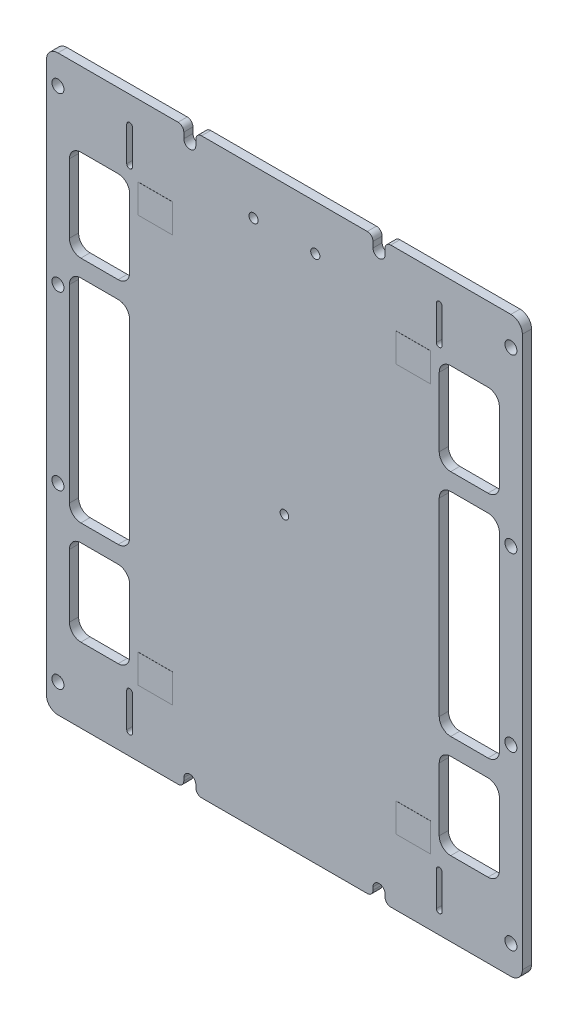
SolidWorks part; units mm, degrees
material "FR4_stuffedProtoboard"
ref_plane "Front Plane" through (0, 0, 0) normal (0, 0, 1) x (1, 0, 0)
ref_plane "Top Plane" through (0, 0, 0) normal (0, 1, 0) x (1, 0, 0)
ref_plane "Right Plane" through (0, 0, 0) normal (1, 0, 0) x (0, 0, -1)
sketch "Sketch1" plane through (0, 0, 0) normal (0, 0, 1) x (1, 0, 0)
  line L1 (-39.5, -50) -> (39.5, -50)
  line L2 (-41.5, -48) -> (-41.5, 48)
  line L3 (-39.5, 50) -> (39.5, 50)
  line L4 (41.5, -48) -> (41.5, 48)
  line L5 (-41.5, -50) -> (41.5, 50) construction
  line L6 (-41.5, 50) -> (41.5, -50) construction
  arc A0 (-39.5, -50) -> (-41.5, -48) centre (-39.5, -48) cw
  arc A1 (39.5, -50) -> (41.5, -48) centre (39.5, -48) ccw
  arc A2 (39.5, 50) -> (41.5, 48) centre (39.5, 48) cw
  arc A3 (-41.5, 48) -> (-39.5, 50) centre (-39.5, 48) cw
  point P0 (0, 0)
  dimension "D3" = 2
  dimension "D1" = 100
  dimension "D2" = 83
extrude "boardOutline" add sketch "Sketch1" along normal blind 1.6
sketch "Sketch2" plane through (0, 0, 1.6) normal (0, 0, 1) x (1, 0, 0)
  line L0 (39.5, 50) -> (-39.5, 50) construction
  line L1 (-41.5, 48) -> (-41.5, -48) construction
  line L2 (-5.385, 42.1) -> (5.385, 42.1) construction
  line L3 (-38, 44.2) -> (-38, 4.2) construction
  line L4 (0, 42.1) -> (0, 50) construction
  circle A0 centre (0, 0) radius 0.75
  circle A1 centre (-38, 44.2) radius 1.05 construction
  circle A2 centre (37.5, 44.2) radius 1.05 construction
  circle A3 centre (37.5, 4.2) radius 1.05 construction
  circle A4 centre (37.5, -35.8) radius 1.05 construction
  circle A5 centre (-38, 4.2) radius 1.05 construction
  circle A6 centre (-38, -35.8) radius 1.05 construction
  circle A7 centre (-5.385, 42.1) radius 0.8
  circle A8 centre (5.385, 42.1) radius 0.8
  dimension "D1" = 1.5
  dimension "D2" = 2.1
  dimension "D9" = 10.77
  dimension "D7" = 1.6
  dimension "D11" = 7.9
  dimension "D3" = 5.8
  dimension "D4" = 3.5
  dimension "D8" = 40
  dimension "D10" = 37.5
  dimension "D5" = 2
  dimension "D6" = 3
extrude "componentHoles" cut sketch "Sketch2" against normal through all
sketch "Sketch4" plane through (0, 0, 1.6) normal (0, 0, 1) x (1, 0, 0)
  line L0 (-27, 39.25) -> (-27, 45.25) construction
  line L1 (-27.5, 39.25) -> (-27.5, 45.25)
  line L2 (-26.5, 39.25) -> (-26.5, 45.25)
  line L3 (39.5, 50) -> (-39.5, 50) construction
  line L4 (-41.5, 48) -> (-41.5, -48) construction
  line L5 (27, 39.25) -> (27, 45.25) construction
  line L6 (26.5, 39.25) -> (26.5, 45.25)
  line L7 (27.5, 39.25) -> (27.5, 45.25)
  line L8 (27, -46.25) -> (27, -40.25) construction
  line L9 (26.5, -46.25) -> (26.5, -40.25)
  line L10 (27.5, -46.25) -> (27.5, -40.25)
  line L11 (-27, -46.25) -> (-27, -40.25) construction
  line L12 (-27.5, -46.25) -> (-27.5, -40.25)
  line L13 (-26.5, -46.25) -> (-26.5, -40.25)
  line L14 (-27, 39.25) -> (27, 39.25) construction
  line L15 (0, 39.25) -> (0, 50) construction
  arc A0 (-27.5, 39.25) -> (-26.5, 39.25) centre (-27, 39.25) ccw
  arc A1 (-26.5, 45.25) -> (-27.5, 45.25) centre (-27, 45.25) ccw
  arc A2 (26.5, 39.25) -> (27.5, 39.25) centre (27, 39.25) ccw
  arc A3 (27.5, 45.25) -> (26.5, 45.25) centre (27, 45.25) ccw
  arc A4 (26.5, -46.25) -> (27.5, -46.25) centre (27, -46.25) ccw
  arc A5 (27.5, -40.25) -> (26.5, -40.25) centre (27, -40.25) ccw
  arc A6 (-27.5, -46.25) -> (-26.5, -46.25) centre (-27, -46.25) ccw
  arc A7 (-26.5, -40.25) -> (-27.5, -40.25) centre (-27, -40.25) ccw
  point P2 (-27, 42.25)
  point P16 (27, 42.25)
  point P23 (27, -43.25)
  point P30 (-27, -43.25)
  dimension "D1" = 4.75
  dimension "D2" = 14
  dimension "D3" = 1
  dimension "D4" = 6
  dimension "D7" = 54
  dimension "D9" = 79.5
  dimension "D5" = 2
  dimension "D6" = 2
extrude "solarCellContactHoles" cut sketch "Sketch4" against normal blind 1.6
sketch "FrameLattice" plane through (0, 0, 0) normal (0, 0, 1) x (1, 0, 0)
  line L4 (-12.5, -19) -> (12.5, -19)
  line L5 (14.5, -17) -> (14.5, 16)
  line L6 (12.5, 18) -> (-12.5, 18)
  line L7 (-14.5, 16) -> (-14.5, -17)
  line L8 (-12.5, -19) -> (12.5, -19)
  line L9 (14.5, -17) -> (14.5, 16)
  line L10 (12.5, 18) -> (-12.5, 18)
  line L11 (-14.5, 16) -> (-14.5, -17)
  line L12 (-12.5, -92) -> (12.5, -92)
  line L13 (14.5, -90) -> (14.5, -69)
  line L14 (12.5, -67) -> (-12.5, -67)
  line L15 (-14.5, -69) -> (-14.5, -90)
  line L16 (-12.5, -92) -> (12.5, -92)
  line L17 (14.5, -90) -> (14.5, -69)
  line L18 (12.5, -67) -> (-12.5, -67)
  line L19 (-14.5, -69) -> (-14.5, -90)
  line L20 (-35.5, -132) -> (-19.5, -132)
  line L21 (-17.5, -130) -> (-17.5, -97)
  line L22 (-19.5, -95) -> (-35.5, -95)
  line L23 (-37.5, -97) -> (-37.5, -130)
  line L24 (-35.5, -132) -> (-19.5, -132)
  line L25 (-17.5, -130) -> (-17.5, -97)
  line L26 (-19.5, -95) -> (-35.5, -95)
  line L27 (-37.5, -97) -> (-37.5, -130)
  line L28 (19.5, -160) -> (35.5, -160)
  line L29 (37.5, -158) -> (37.5, -137)
  line L30 (35.5, -135) -> (19.5, -135)
  line L31 (17.5, -137) -> (17.5, -158)
  line L32 (19.5, -160) -> (35.5, -160)
  line L33 (37.5, -158) -> (37.5, -137)
  line L34 (35.5, -135) -> (19.5, -135)
  line L35 (17.5, -137) -> (17.5, -158)
  line L36 (19.5, -92) -> (35.5, -92)
  line L37 (37.5, -90) -> (37.5, -69)
  line L38 (35.5, -67) -> (19.5, -67)
  line L39 (17.5, -69) -> (17.5, -90)
  line L40 (19.5, -92) -> (35.5, -92)
  line L41 (37.5, -90) -> (37.5, -69)
  line L42 (35.5, -67) -> (19.5, -67)
  line L43 (17.5, -69) -> (17.5, -90)
  line L44 (-35.5, -92) -> (-19.5, -92)
  line L45 (-17.5, -90) -> (-17.5, -69)
  line L46 (-19.5, -67) -> (-35.5, -67)
  line L47 (-37.5, -69) -> (-37.5, -90)
  line L48 (-35.5, -92) -> (-19.5, -92)
  line L49 (-17.5, -90) -> (-17.5, -69)
  line L50 (-19.5, -67) -> (-35.5, -67)
  line L51 (-37.5, -69) -> (-37.5, -90)
  line L52 (19.5, -132) -> (35.5, -132)
  line L53 (37.5, -130) -> (37.5, -97)
  line L54 (35.5, -95) -> (19.5, -95)
  line L55 (17.5, -97) -> (17.5, -130)
  line L56 (19.5, -132) -> (35.5, -132)
  line L57 (37.5, -130) -> (37.5, -97)
  line L58 (35.5, -95) -> (19.5, -95)
  line L59 (17.5, -97) -> (17.5, -130)
  line L60 (-12.5, -160) -> (12.5, -160)
  line L61 (14.5, -158) -> (14.5, -137)
  line L62 (12.5, -135) -> (-12.5, -135)
  line L63 (-14.5, -137) -> (-14.5, -158)
  line L65 (14.5, -158) -> (14.5, -137)
  line L66 (12.5, -135) -> (-12.5, -135)
  line L67 (-14.5, -137) -> (-14.5, -158)
  line L68 (-26.75, -62) -> (-26.75, -52)
  line L69 (-28.75, -50) -> (-35, -50)
  line L70 (-37, -52) -> (-37, -62)
  line L71 (-35, -64) -> (-28.75, -64)
  line L72 (-26.75, -62) -> (-26.75, -52)
  line L73 (-28.75, -50) -> (-35, -50)
  line L74 (-37, -52) -> (-37, -62)
  line L75 (-35, -64) -> (-28.75, -64)
  line L76 (-35.5, -160) -> (-19.5, -160)
  line L77 (-17.5, -158) -> (-17.5, -137)
  line L78 (-19.5, -135) -> (-35.5, -135)
  line L79 (-37.5, -137) -> (-37.5, -158)
  line L80 (-35.5, -160) -> (-19.5, -160)
  line L81 (-17.5, -158) -> (-17.5, -137)
  line L82 (-19.5, -135) -> (-35.5, -135)
  line L83 (-37.5, -137) -> (-37.5, -158)
  line L84 (-12.5, -132) -> (12.5, -132)
  line L85 (14.5, -130) -> (14.5, -97)
  line L86 (12.5, -95) -> (-12.5, -95)
  line L87 (-14.5, -97) -> (-14.5, -130)
  line L88 (-12.5, -132) -> (12.5, -132)
  line L89 (14.5, -130) -> (14.5, -97)
  line L90 (12.5, -95) -> (-12.5, -95)
  line L91 (-14.5, -97) -> (-14.5, -130)
  line L92 (-35.5, -19) -> (-19.5, -19)
  line L93 (-17.5, -17) -> (-17.5, 16)
  line L94 (-19.5, 18) -> (-35.5, 18)
  line L95 (-37.5, 16) -> (-37.5, -17)
  line L96 (-35.5, -19) -> (-19.5, -19)
  line L97 (-17.5, -17) -> (-17.5, 16)
  line L98 (-19.5, 18) -> (-35.5, 18)
  line L99 (-37.5, 16) -> (-37.5, -17)
  line L100 (19.5, -47) -> (35.5, -47)
  line L101 (37.5, -45) -> (37.5, -24)
  line L102 (35.5, -22) -> (19.5, -22)
  line L103 (17.5, -24) -> (17.5, -45)
  line L104 (19.5, -47) -> (35.5, -47)
  line L105 (37.5, -45) -> (37.5, -24)
  line L106 (35.5, -22) -> (19.5, -22)
  line L107 (17.5, -24) -> (17.5, -45)
  line L108 (-12.5, -47) -> (12.5, -47)
  line L109 (14.5, -45) -> (14.5, -24)
  line L110 (12.5, -22) -> (-12.5, -22)
  line L111 (-14.5, -24) -> (-14.5, -45)
  line L112 (-12.5, -47) -> (12.5, -47)
  line L113 (14.5, -45) -> (14.5, -24)
  line L114 (12.5, -22) -> (-12.5, -22)
  line L115 (-14.5, -24) -> (-14.5, -45)
  line L116 (-35.5, -47) -> (-19.5, -47)
  line L117 (-17.5, -45) -> (-17.5, -24)
  line L118 (-19.5, -22) -> (-35.5, -22)
  line L119 (-37.5, -24) -> (-37.5, -45)
  line L120 (-35.5, -47) -> (-19.5, -47)
  line L121 (-17.5, -45) -> (-17.5, -24)
  line L122 (-19.5, -22) -> (-35.5, -22)
  line L123 (-37.5, -24) -> (-37.5, -45)
  line L124 (19.5, -19) -> (35.5, -19)
  line L125 (37.5, -17) -> (37.5, 16)
  line L126 (35.5, 18) -> (19.5, 18)
  line L127 (17.5, 16) -> (17.5, -17)
  line L128 (19.5, -19) -> (35.5, -19)
  line L129 (37.5, -17) -> (37.5, 16)
  line L130 (35.5, 18) -> (19.5, 18)
  line L131 (17.5, 16) -> (17.5, -17)
  line L132 (-35.5, 21) -> (-19.5, 21)
  line L133 (-17.5, 23) -> (-17.5, 44)
  line L134 (-19.5, 46) -> (-35.5, 46)
  line L135 (-37.5, 44) -> (-37.5, 23)
  line L136 (-35.5, 21) -> (-19.5, 21)
  line L137 (-17.5, 23) -> (-17.5, 44)
  line L138 (-19.5, 46) -> (-35.5, 46)
  line L139 (-37.5, 44) -> (-37.5, 23)
  line L140 (-12.5, 21) -> (12.5, 21)
  line L141 (14.5, 23) -> (14.5, 44)
  line L142 (12.5, 46) -> (-12.5, 46)
  line L143 (-14.5, 44) -> (-14.5, 23)
  line L144 (-12.5, 21) -> (12.5, 21)
  line L145 (14.5, 23) -> (14.5, 44)
  line L147 (-14.5, 44) -> (-14.5, 23)
  line L148 (19.5, 21) -> (35.5, 21)
  line L149 (37.5, 23) -> (37.5, 44)
  line L150 (35.5, 46) -> (19.5, 46)
  line L151 (17.5, 44) -> (17.5, 23)
  line L152 (19.5, 21) -> (35.5, 21)
  line L153 (37.5, 23) -> (37.5, 44)
  line L154 (35.5, 46) -> (19.5, 46)
  line L155 (17.5, 44) -> (17.5, 23)
  line L156 (-3.5, -62) -> (-3.5, -52)
  line L157 (-5.5, -50) -> (-13, -50)
  line L158 (-15, -52) -> (-15, -62)
  line L159 (-13, -64) -> (-5.5, -64)
  line L160 (-3.5, -62) -> (-3.5, -52)
  line L161 (-5.5, -50) -> (-13, -50)
  line L162 (-15, -52) -> (-15, -62)
  line L163 (-13, -64) -> (-5.5, -64)
  line L164 (28.75, -64) -> (35, -64)
  line L165 (37, -62) -> (37, -52)
  line L166 (35, -50) -> (28.75, -50)
  line L167 (26.75, -52) -> (26.75, -62)
  line L168 (28.75, -64) -> (35, -64)
  line L169 (37, -62) -> (37, -52)
  line L170 (35, -50) -> (28.75, -50)
  line L171 (26.75, -52) -> (26.75, -62)
  line L172 (5.5, -64) -> (13, -64)
  line L173 (15, -62) -> (15, -52)
  line L174 (13, -50) -> (5.5, -50)
  line L175 (3.5, -52) -> (3.5, -62)
  line L176 (5.5, -64) -> (13, -64)
  line L177 (15, -62) -> (15, -52)
  line L178 (13, -50) -> (5.5, -50)
  line L179 (3.5, -52) -> (3.5, -62)
  line L212 (-12.5, -160) -> (12.5, -160)
  line L213 (12.5, 46) -> (-12.5, 46)
  circle A2 centre (-16.5, 48) radius 0.8
  circle A3 centre (-16.5, 48) radius 0.8
  circle A4 centre (-16.5, -162) radius 0.8
  arc A5 (12.5, -19) -> (14.5, -17) centre (12.5, -17) ccw
  arc A6 (14.5, 16) -> (12.5, 18) centre (12.5, 16) ccw
  arc A7 (-12.5, 18) -> (-14.5, 16) centre (-12.5, 16) ccw
  arc A8 (-14.5, -17) -> (-12.5, -19) centre (-12.5, -17) ccw
  arc A9 (12.5, -19) -> (14.5, -17) centre (12.5, -17) ccw
  arc A10 (14.5, 16) -> (12.5, 18) centre (12.5, 16) ccw
  arc A11 (-12.5, 18) -> (-14.5, 16) centre (-12.5, 16) ccw
  arc A12 (-14.5, -17) -> (-12.5, -19) centre (-12.5, -17) ccw
  arc A13 (12.5, -92) -> (14.5, -90) centre (12.5, -90) ccw
  arc A14 (14.5, -69) -> (12.5, -67) centre (12.5, -69) ccw
  arc A15 (-12.5, -67) -> (-14.5, -69) centre (-12.5, -69) ccw
  arc A16 (-14.5, -90) -> (-12.5, -92) centre (-12.5, -90) ccw
  arc A17 (12.5, -92) -> (14.5, -90) centre (12.5, -90) ccw
  arc A18 (14.5, -69) -> (12.5, -67) centre (12.5, -69) ccw
  arc A19 (-12.5, -67) -> (-14.5, -69) centre (-12.5, -69) ccw
  arc A20 (-14.5, -90) -> (-12.5, -92) centre (-12.5, -90) ccw
  arc A21 (-19.5, -132) -> (-17.5, -130) centre (-19.5, -130) ccw
  arc A22 (-17.5, -97) -> (-19.5, -95) centre (-19.5, -97) ccw
  arc A23 (-35.5, -95) -> (-37.5, -97) centre (-35.5, -97) ccw
  arc A24 (-37.5, -130) -> (-35.5, -132) centre (-35.5, -130) ccw
  arc A25 (-19.5, -132) -> (-17.5, -130) centre (-19.5, -130) ccw
  arc A26 (-17.5, -97) -> (-19.5, -95) centre (-19.5, -97) ccw
  arc A27 (-35.5, -95) -> (-37.5, -97) centre (-35.5, -97) ccw
  arc A28 (-37.5, -130) -> (-35.5, -132) centre (-35.5, -130) ccw
  arc A29 (35.5, -160) -> (37.5, -158) centre (35.5, -158) ccw
  arc A30 (37.5, -137) -> (35.5, -135) centre (35.5, -137) ccw
  arc A31 (19.5, -135) -> (17.5, -137) centre (19.5, -137) ccw
  arc A32 (17.5, -158) -> (19.5, -160) centre (19.5, -158) ccw
  arc A33 (35.5, -160) -> (37.5, -158) centre (35.5, -158) ccw
  arc A34 (37.5, -137) -> (35.5, -135) centre (35.5, -137) ccw
  arc A35 (19.5, -135) -> (17.5, -137) centre (19.5, -137) ccw
  arc A36 (17.5, -158) -> (19.5, -160) centre (19.5, -158) ccw
  arc A37 (35.5, -92) -> (37.5, -90) centre (35.5, -90) ccw
  arc A38 (37.5, -69) -> (35.5, -67) centre (35.5, -69) ccw
  arc A39 (19.5, -67) -> (17.5, -69) centre (19.5, -69) ccw
  arc A40 (17.5, -90) -> (19.5, -92) centre (19.5, -90) ccw
  arc A41 (35.5, -92) -> (37.5, -90) centre (35.5, -90) ccw
  arc A42 (37.5, -69) -> (35.5, -67) centre (35.5, -69) ccw
  arc A43 (19.5, -67) -> (17.5, -69) centre (19.5, -69) ccw
  arc A44 (17.5, -90) -> (19.5, -92) centre (19.5, -90) ccw
  arc A45 (-19.5, -92) -> (-17.5, -90) centre (-19.5, -90) ccw
  arc A46 (-17.5, -69) -> (-19.5, -67) centre (-19.5, -69) ccw
  arc A47 (-35.5, -67) -> (-37.5, -69) centre (-35.5, -69) ccw
  arc A48 (-37.5, -90) -> (-35.5, -92) centre (-35.5, -90) ccw
  arc A49 (-19.5, -92) -> (-17.5, -90) centre (-19.5, -90) ccw
  arc A50 (-17.5, -69) -> (-19.5, -67) centre (-19.5, -69) ccw
  arc A51 (-35.5, -67) -> (-37.5, -69) centre (-35.5, -69) ccw
  arc A52 (-37.5, -90) -> (-35.5, -92) centre (-35.5, -90) ccw
  arc A53 (35.5, -132) -> (37.5, -130) centre (35.5, -130) ccw
  arc A54 (37.5, -97) -> (35.5, -95) centre (35.5, -97) ccw
  arc A55 (19.5, -95) -> (17.5, -97) centre (19.5, -97) ccw
  arc A56 (17.5, -130) -> (19.5, -132) centre (19.5, -130) ccw
  arc A57 (35.5, -132) -> (37.5, -130) centre (35.5, -130) ccw
  arc A58 (37.5, -97) -> (35.5, -95) centre (35.5, -97) ccw
  arc A59 (19.5, -95) -> (17.5, -97) centre (19.5, -97) ccw
  arc A60 (17.5, -130) -> (19.5, -132) centre (19.5, -130) ccw
  arc A61 (12.5, -160) -> (14.5, -158) centre (12.5, -158) ccw
  arc A62 (14.5, -137) -> (12.5, -135) centre (12.5, -137) ccw
  arc A63 (-12.5, -135) -> (-14.5, -137) centre (-12.5, -137) ccw
  arc A64 (-14.5, -158) -> (-12.5, -160) centre (-12.5, -158) ccw
  arc A65 (12.5, -160) -> (14.5, -158) centre (12.5, -158) ccw
  arc A66 (14.5, -137) -> (12.5, -135) centre (12.5, -137) ccw
  arc A67 (-12.5, -135) -> (-14.5, -137) centre (-12.5, -137) ccw
  arc A68 (-14.5, -158) -> (-12.5, -160) centre (-12.5, -158) ccw
  circle A69 centre (-16.5, -162) radius 0.8
  circle A70 centre (16.5, -162) radius 0.8
  circle A71 centre (16.5, -162) radius 0.8
  circle A72 centre (-16.5, -65.5) radius 0.8
  circle A73 centre (-16.5, -65.5) radius 0.8
  circle A74 centre (16.5, -65.5) radius 0.8
  circle A75 centre (16.5, -65.5) radius 0.8
  circle A76 centre (-39.5, -129) radius 0.8
  circle A77 centre (-39.5, -129) radius 0.8
  circle A78 centre (39.5, -159) radius 0.8
  circle A79 centre (39.5, -159) radius 0.8
  circle A80 centre (-39.5, -159) radius 0.8
  circle A81 centre (-39.5, -159) radius 0.8
  circle A82 centre (39.5, -129) radius 0.8
  circle A83 centre (39.5, -129) radius 0.8
  circle A84 centre (39.5, -99) radius 0.8
  circle A85 centre (39.5, -99) radius 0.8
  circle A86 centre (-39.5, -99) radius 0.8
  circle A87 centre (-39.5, -99) radius 0.8
  circle A88 centre (-39.5, -69) radius 0.8
  circle A89 centre (-39.5, -69) radius 0.8
  circle A90 centre (39.5, -69) radius 0.8
  circle A91 centre (39.5, -69) radius 0.8
  circle A92 centre (39.5, -15) radius 0.8
  circle A93 centre (39.5, -15) radius 0.8
  circle A94 centre (39.5, 15) radius 0.8
  arc A95 (-26.75, -52) -> (-28.75, -50) centre (-28.75, -52) ccw
  arc A96 (-35, -50) -> (-37, -52) centre (-35, -52) ccw
  arc A97 (-37, -62) -> (-35, -64) centre (-35, -62) ccw
  arc A98 (-28.75, -64) -> (-26.75, -62) centre (-28.75, -62) ccw
  arc A99 (-26.75, -52) -> (-28.75, -50) centre (-28.75, -52) ccw
  arc A100 (-35, -50) -> (-37, -52) centre (-35, -52) ccw
  arc A101 (-37, -62) -> (-35, -64) centre (-35, -62) ccw
  arc A102 (-28.75, -64) -> (-26.75, -62) centre (-28.75, -62) ccw
  arc A103 (-19.5, -160) -> (-17.5, -158) centre (-19.5, -158) ccw
  arc A104 (-17.5, -137) -> (-19.5, -135) centre (-19.5, -137) ccw
  arc A105 (-35.5, -135) -> (-37.5, -137) centre (-35.5, -137) ccw
  arc A106 (-37.5, -158) -> (-35.5, -160) centre (-35.5, -158) ccw
  arc A107 (-19.5, -160) -> (-17.5, -158) centre (-19.5, -158) ccw
  arc A108 (-17.5, -137) -> (-19.5, -135) centre (-19.5, -137) ccw
  arc A109 (-35.5, -135) -> (-37.5, -137) centre (-35.5, -137) ccw
  arc A110 (-37.5, -158) -> (-35.5, -160) centre (-35.5, -158) ccw
  arc A111 (12.5, -132) -> (14.5, -130) centre (12.5, -130) ccw
  arc A112 (14.5, -97) -> (12.5, -95) centre (12.5, -97) ccw
  arc A113 (-12.5, -95) -> (-14.5, -97) centre (-12.5, -97) ccw
  arc A114 (-14.5, -130) -> (-12.5, -132) centre (-12.5, -130) ccw
  arc A115 (12.5, -132) -> (14.5, -130) centre (12.5, -130) ccw
  arc A116 (14.5, -97) -> (12.5, -95) centre (12.5, -97) ccw
  arc A117 (-12.5, -95) -> (-14.5, -97) centre (-12.5, -97) ccw
  arc A118 (-14.5, -130) -> (-12.5, -132) centre (-12.5, -130) ccw
  arc A119 (-19.5, -19) -> (-17.5, -17) centre (-19.5, -17) ccw
  arc A120 (-17.5, 16) -> (-19.5, 18) centre (-19.5, 16) ccw
  arc A121 (-35.5, 18) -> (-37.5, 16) centre (-35.5, 16) ccw
  arc A122 (-37.5, -17) -> (-35.5, -19) centre (-35.5, -17) ccw
  arc A123 (-19.5, -19) -> (-17.5, -17) centre (-19.5, -17) ccw
  arc A124 (-17.5, 16) -> (-19.5, 18) centre (-19.5, 16) ccw
  arc A125 (-35.5, 18) -> (-37.5, 16) centre (-35.5, 16) ccw
  arc A126 (-37.5, -17) -> (-35.5, -19) centre (-35.5, -17) ccw
  arc A127 (35.5, -47) -> (37.5, -45) centre (35.5, -45) ccw
  arc A128 (37.5, -24) -> (35.5, -22) centre (35.5, -24) ccw
  arc A129 (19.5, -22) -> (17.5, -24) centre (19.5, -24) ccw
  arc A130 (17.5, -45) -> (19.5, -47) centre (19.5, -45) ccw
  arc A131 (35.5, -47) -> (37.5, -45) centre (35.5, -45) ccw
  arc A132 (37.5, -24) -> (35.5, -22) centre (35.5, -24) ccw
  arc A133 (19.5, -22) -> (17.5, -24) centre (19.5, -24) ccw
  arc A134 (17.5, -45) -> (19.5, -47) centre (19.5, -45) ccw
  arc A135 (12.5, -47) -> (14.5, -45) centre (12.5, -45) ccw
  arc A136 (14.5, -24) -> (12.5, -22) centre (12.5, -24) ccw
  arc A137 (-12.5, -22) -> (-14.5, -24) centre (-12.5, -24) ccw
  arc A138 (-14.5, -45) -> (-12.5, -47) centre (-12.5, -45) ccw
  arc A139 (12.5, -47) -> (14.5, -45) centre (12.5, -45) ccw
  arc A140 (14.5, -24) -> (12.5, -22) centre (12.5, -24) ccw
  arc A141 (-12.5, -22) -> (-14.5, -24) centre (-12.5, -24) ccw
  arc A142 (-14.5, -45) -> (-12.5, -47) centre (-12.5, -45) ccw
  arc A143 (-19.5, -47) -> (-17.5, -45) centre (-19.5, -45) ccw
  arc A144 (-17.5, -24) -> (-19.5, -22) centre (-19.5, -24) ccw
  arc A145 (-35.5, -22) -> (-37.5, -24) centre (-35.5, -24) ccw
  arc A146 (-37.5, -45) -> (-35.5, -47) centre (-35.5, -45) ccw
  arc A147 (-19.5, -47) -> (-17.5, -45) centre (-19.5, -45) ccw
  arc A148 (-17.5, -24) -> (-19.5, -22) centre (-19.5, -24) ccw
  arc A149 (-35.5, -22) -> (-37.5, -24) centre (-35.5, -24) ccw
  arc A150 (-37.5, -45) -> (-35.5, -47) centre (-35.5, -45) ccw
  arc A151 (35.5, -19) -> (37.5, -17) centre (35.5, -17) ccw
  arc A152 (37.5, 16) -> (35.5, 18) centre (35.5, 16) ccw
  arc A153 (19.5, 18) -> (17.5, 16) centre (19.5, 16) ccw
  arc A154 (17.5, -17) -> (19.5, -19) centre (19.5, -17) ccw
  arc A155 (35.5, -19) -> (37.5, -17) centre (35.5, -17) ccw
  arc A156 (37.5, 16) -> (35.5, 18) centre (35.5, 16) ccw
  arc A157 (19.5, 18) -> (17.5, 16) centre (19.5, 16) ccw
  arc A158 (17.5, -17) -> (19.5, -19) centre (19.5, -17) ccw
  arc A159 (-19.5, 21) -> (-17.5, 23) centre (-19.5, 23) ccw
  arc A160 (-17.5, 44) -> (-19.5, 46) centre (-19.5, 44) ccw
  arc A161 (-35.5, 46) -> (-37.5, 44) centre (-35.5, 44) ccw
  arc A162 (-37.5, 23) -> (-35.5, 21) centre (-35.5, 23) ccw
  arc A163 (-19.5, 21) -> (-17.5, 23) centre (-19.5, 23) ccw
  arc A164 (-17.5, 44) -> (-19.5, 46) centre (-19.5, 44) ccw
  arc A165 (-35.5, 46) -> (-37.5, 44) centre (-35.5, 44) ccw
  arc A166 (-37.5, 23) -> (-35.5, 21) centre (-35.5, 23) ccw
  arc A167 (12.5, 21) -> (14.5, 23) centre (12.5, 23) ccw
  arc A168 (14.5, 44) -> (12.5, 46) centre (12.5, 44) ccw
  arc A169 (-12.5, 46) -> (-14.5, 44) centre (-12.5, 44) ccw
  arc A170 (-14.5, 23) -> (-12.5, 21) centre (-12.5, 23) ccw
  arc A171 (12.5, 21) -> (14.5, 23) centre (12.5, 23) ccw
  arc A172 (14.5, 44) -> (12.5, 46) centre (12.5, 44) ccw
  arc A173 (-12.5, 46) -> (-14.5, 44) centre (-12.5, 44) ccw
  arc A174 (-14.5, 23) -> (-12.5, 21) centre (-12.5, 23) ccw
  arc A175 (35.5, 21) -> (37.5, 23) centre (35.5, 23) ccw
  arc A176 (37.5, 44) -> (35.5, 46) centre (35.5, 44) ccw
  arc A177 (19.5, 46) -> (17.5, 44) centre (19.5, 44) ccw
  arc A178 (17.5, 23) -> (19.5, 21) centre (19.5, 23) ccw
  arc A179 (35.5, 21) -> (37.5, 23) centre (35.5, 23) ccw
  arc A180 (37.5, 44) -> (35.5, 46) centre (35.5, 44) ccw
  arc A181 (19.5, 46) -> (17.5, 44) centre (19.5, 44) ccw
  arc A182 (17.5, 23) -> (19.5, 21) centre (19.5, 23) ccw
  circle A183 centre (39.5, 15) radius 0.8
  circle A184 centre (-39.5, 45) radius 0.8
  circle A185 centre (-39.5, 45) radius 0.8
  circle A186 centre (39.5, 45) radius 0.8
  circle A187 centre (39.5, 45) radius 0.8
  circle A188 centre (-39.5, 15) radius 0.8
  circle A189 centre (-39.5, 15) radius 0.8
  circle A190 centre (16.5, -48.5) radius 0.8
  circle A191 centre (16.5, -48.5) radius 0.8
  circle A192 centre (-16.5, -48.5) radius 0.8
  circle A193 centre (-16.5, -48.5) radius 0.8
  circle A194 centre (16.5, 48) radius 0.8
  circle A195 centre (16.5, 48) radius 0.8
  circle A196 centre (-39.5, -15) radius 0.8
  circle A197 centre (-39.5, -15) radius 0.8
  circle A198 centre (-22, -61) radius 2.75
  circle A199 centre (-22, -61) radius 2.75
  circle A200 centre (-22, -53) radius 2.75
  circle A201 centre (-22, -53) radius 2.75
  circle A202 centre (22, -53) radius 2.75
  circle A203 centre (22, -53) radius 2.75
  circle A204 centre (22, -61) radius 2.75
  arc A205 (-3.5, -52) -> (-5.5, -50) centre (-5.5, -52) ccw
  arc A206 (-13, -50) -> (-15, -52) centre (-13, -52) ccw
  arc A207 (-15, -62) -> (-13, -64) centre (-13, -62) ccw
  arc A208 (-5.5, -64) -> (-3.5, -62) centre (-5.5, -62) ccw
  arc A209 (-3.5, -52) -> (-5.5, -50) centre (-5.5, -52) ccw
  arc A210 (-13, -50) -> (-15, -52) centre (-13, -52) ccw
  arc A211 (-15, -62) -> (-13, -64) centre (-13, -62) ccw
  arc A212 (-5.5, -64) -> (-3.5, -62) centre (-5.5, -62) ccw
  circle A213 centre (22, -61) radius 2.75
  circle A214 centre (0, -57) radius 2.75
  circle A215 centre (0, -57) radius 2.75
  circle A216 centre (39.5, -45) radius 0.8
  circle A217 centre (39.5, -45) radius 0.8
  circle A218 centre (-39.5, -45) radius 0.8
  arc A219 (35, -64) -> (37, -62) centre (35, -62) ccw
  arc A220 (37, -52) -> (35, -50) centre (35, -52) ccw
  arc A221 (28.75, -50) -> (26.75, -52) centre (28.75, -52) ccw
  arc A222 (26.75, -62) -> (28.75, -64) centre (28.75, -62) ccw
  arc A223 (35, -64) -> (37, -62) centre (35, -62) ccw
  arc A224 (37, -52) -> (35, -50) centre (35, -52) ccw
  arc A225 (28.75, -50) -> (26.75, -52) centre (28.75, -52) ccw
  arc A226 (26.75, -62) -> (28.75, -64) centre (28.75, -62) ccw
  arc A227 (13, -64) -> (15, -62) centre (13, -62) ccw
  arc A228 (15, -52) -> (13, -50) centre (13, -52) ccw
  arc A229 (5.5, -50) -> (3.5, -52) centre (5.5, -52) ccw
  arc A230 (3.5, -62) -> (5.5, -64) centre (5.5, -62) ccw
  arc A231 (13, -64) -> (15, -62) centre (13, -62) ccw
  arc A232 (15, -52) -> (13, -50) centre (13, -52) ccw
  arc A233 (5.5, -50) -> (3.5, -52) centre (5.5, -52) ccw
  arc A234 (3.5, -62) -> (5.5, -64) centre (5.5, -62) ccw
  circle A235 centre (-39.5, -45) radius 0.8
  dimension "D1" = 0
  dimension "D2" = 0
  dimension "D3" = 0
  dimension "D4" = 0
  dimension "D5" = 0
  dimension "D6" = 0
  dimension "D7" = 0
  dimension "D8" = 0
  dimension "D9" = 0
  dimension "D10" = 0
  dimension "D11" = 0
  dimension "D12" = 0
  dimension "D13" = 0
  dimension "D14" = 0
  dimension "D15" = 0
  dimension "D16" = 0
  dimension "D17" = 0
  dimension "D18" = 0
  dimension "D19" = 0
  dimension "D20" = 0
  dimension "D21" = 0
  dimension "D22" = 0
  dimension "D23" = 0
  dimension "D24" = 0
  dimension "D25" = 0
  dimension "D26" = 0
  dimension "D27" = 0
  dimension "D28" = 0
  dimension "D29" = 0
  dimension "D30" = 0
  dimension "D31" = 0
  dimension "D32" = 0
  dimension "D33" = 0
  dimension "D34" = 0
  dimension "D35" = 0
  dimension "D36" = 0
  dimension "D37" = 0
  dimension "D38" = 0
  dimension "D39" = 0
  dimension "D40" = 0
  dimension "D41" = 0
  dimension "D42" = 0
  dimension "D43" = 0
  dimension "D44" = 0
  dimension "D45" = 0
  dimension "D46" = 0
  dimension "D47" = 0
  dimension "D48" = 0
  dimension "D49" = 0
  dimension "D50" = 0
  dimension "D51" = 0
sketch "Sketch3" plane through (0, 0, 1.6) normal (0, 0, 1) x (1, 0, 0)
  line L0 (-35.5, -19) -> (-19.5, -19) construction
  line L1 (-35.5, 37) -> (-29, 37)
  line L2 (-37.5, 35) -> (-37.5, 23)
  line L3 (-35.5, 21) -> (-29, 21)
  line L4 (-27, 35) -> (-27, 23)
  line L6 (-29, -22) -> (-35.5, -22)
  line L7 (-37.5, 16) -> (-37.5, -17) construction
  line L8 (-19.5, -22) -> (-35.5, -22) construction
  line L9 (0, 50) -> (0, -50) construction
  line L10 (39.5, 50) -> (-39.5, 50) construction
  line L11 (-39.5, -50) -> (39.5, -50) construction
  line L12 (-27, -24) -> (-27, -35)
  line L13 (-29, -37) -> (-35.5, -37)
  line L14 (-37.5, -24) -> (-37.5, -35)
  line L15 (-19.5, 18) -> (-35.5, 18) construction
  line L16 (-35.5, 21) -> (-19.5, 21) construction
  line L19 (-29, -19) -> (-35.5, -19)
  line L25 (-27, -17) -> (-27, 16)
  line L26 (-29, 18) -> (-35.5, 18)
  line L27 (-37.5, -17) -> (-37.5, 16)
  arc A0 (-37.5, 23) -> (-35.5, 21) centre (-35.5, 23) ccw
  arc A1 (-29, 21) -> (-27, 23) centre (-29, 23) ccw
  arc A2 (-29, 37) -> (-27, 35) centre (-29, 35) cw
  arc A3 (-35.5, 37) -> (-37.5, 35) centre (-35.5, 35) ccw
  arc A4 (-29, -19) -> (-27, -17) centre (-29, -17) ccw
  arc A5 (-27, -35) -> (-29, -37) centre (-29, -35) cw
  arc A6 (-35.5, -37) -> (-37.5, -35) centre (-35.5, -35) cw
  arc A7 (-35.5, -22) -> (-37.5, -24) centre (-35.5, -24) ccw
  arc A8 (-29, -22) -> (-27, -24) centre (-29, -24) cw
  arc A9 (-37.5, 23) -> (-35.5, 21) centre (-35.5, 23) ccw construction
  arc A17 (-35.5, -19) -> (-37.5, -17) centre (-35.5, -17) cw
  arc A18 (-35.5, 18) -> (-37.5, 16) centre (-35.5, 16) ccw
  arc A19 (-27, 16) -> (-29, 18) centre (-29, 16) ccw
  point P12 (-27, 21)
  point P15 (-27, 37)
  point P18 (-37.5, 37)
  dimension "D10" = 13
  dimension "D1" = 10.5
  dimension "D3" = 13
extrude "windows_1side" cut sketch "Sketch3" against normal through all
sketch "Sketch5" plane through (0, 0, 1.6) normal (0, 0, 1) x (1, 0, 0)
  line L0 (-41.5, 48) -> (-41.5, -48) construction
  line L1 (-25.5, 37.5) -> (-19.5, 37.5)
  line L2 (-25.5, 37.5) -> (-25.5, 32.5)
  line L3 (-25.5, 32.5) -> (-19.5, 32.5)
  line L4 (-19.5, 37.5) -> (-19.5, 32.5)
  line L5 (0, 37.5) -> (0, 50) construction
  line L6 (19.5, 37.5) -> (19.5, 32.5)
  line L7 (25.5, 37.5) -> (25.5, 32.5)
  line L8 (19.5, 32.5) -> (25.5, 32.5)
  line L9 (19.5, 37.5) -> (25.5, 37.5)
  line L10 (19.5, -33.5) -> (19.5, -38.5)
  line L11 (25.5, -33.5) -> (25.5, -38.5)
  line L12 (19.5, -38.5) -> (25.5, -38.5)
  line L13 (19.5, -33.5) -> (25.5, -33.5)
  line L14 (-25.5, -33.5) -> (-25.5, -38.5)
  line L15 (-19.5, -33.5) -> (-19.5, -38.5)
  line L16 (-25.5, -38.5) -> (-19.5, -38.5)
  line L17 (-25.5, -33.5) -> (-19.5, -33.5)
  line L18 (-19.5, 37.5) -> (19.5, 37.5) construction
  line L19 (-25.5, 37.5) -> (-25.5, -33.5) construction
  line L20 (39.5, 50) -> (-39.5, 50) construction
  arc A0 (-27.5, 39.25) -> (-26.5, 39.25) centre (-27, 39.25) ccw construction
  dimension "D1" = 5
  dimension "D2" = 6
  dimension "D3" = 16
  dimension "D4" = 1.75
  dimension "D7" = 45
  dimension "D8" = 71
  dimension "D5" = 2
  dimension "D6" = 2
extrude "contactPads" add sketch "Sketch5" along normal blind 0.02
hole_wizard "M2 Clearance Hole1" positions "Sketch6" profile "Sketch7" hole size "M2" standard "ANSI Metric" end condition through all
sketch "Sketch6" plane through (0, 0, 0) normal (0, 0, -1) x (-1, 0, 0)
  line L5 (39.5, -50) -> (39.5, -45) construction
  line L6 (39.5, -50) -> (-39.5, -50) construction
  line L7 (39.5, -45) -> (39.5, -15) construction
  line L8 (39.5, -15) -> (39.5, 15) construction
  line L9 (39.5, 15) -> (39.5, 45) construction
  line L10 (39.5, 45) -> (39.5, 50) construction
  line L11 (-39.5, 50) -> (39.5, 50) construction
  line L15 (37.5, -27.0602) -> (41.5, -27.0602) construction
  line L16 (37.5, -24) -> (37.5, -35) construction
  line L17 (41.5, 48) -> (41.5, -48) construction
  point P0 (39.5, 45)
  point P27 (39.5, -15)
  point P36 (39.5, -45)
  point P38 (39.5, 15)
  point P73 (39.5, -27.0602)
  dimension "D2" = 5
sketch "Sketch7" plane through (-39.5, 45, 0) normal (1, 0, 0) x (0, 1, 0)
  line L0 (0, 0) -> (0, 1.62)
  line L1 (0, 1.62) -> (1.05, 1.62)
  line L2 (1.05, 1.62) -> (1.05, 0)
  line L5 (1.05, 0) -> (0, 0)
  line L11 (0, -6.35) -> (0, 107.95) construction
  dimension "Thru Hole Dia." = 2.1
  dimension "Thru Hole Depth" = 1.62
sketch "Sketch10" plane through (0, 0, 0) normal (0, 0, -1) x (-1, 0, 0)
  line L0 (16.5, 48) -> (16.5, 55.0732) construction
  line L1 (15.45, 48) -> (15.45, 55.0732)
  line L2 (17.55, 48) -> (17.55, 55.0732)
  line L3 (16.5, -48.5) -> (16.5, -55.5732) construction
  line L4 (17.55, -48.5) -> (17.55, -55.5732)
  line L5 (15.45, -48.5) -> (15.45, -55.5732)
  line L6 (41.5, 48) -> (41.5, -48) construction
  line L8 (39.5, -50) -> (-39.5, -50) construction
  line L9 (-39.5, 50) -> (39.5, 50) construction
  arc A0 (15.45, 48) -> (17.55, 48) centre (16.5, 48) ccw
  arc A1 (17.55, 55.0732) -> (15.45, 55.0732) centre (16.5, 55.0732) ccw
  arc A2 (17.55, -48.5) -> (15.45, -48.5) centre (16.5, -48.5) ccw
  arc A3 (15.45, -55.5732) -> (17.55, -55.5732) centre (16.5, -55.5732) ccw
  point P2 (16.5, 51.5366)
  point P7 (16.5, -52.0366)
  dimension "D1" = 1.05
  dimension "D2" = 25
  dimension "D3" = 2
  dimension "D4" = 1.5
extrude "Cut-Extrude1" cut sketch "Sketch10" against normal through all both and the other way through all
fillet "Fillet3" radius 1 4 edges at (-17.55, 50, 0.8) (-15.45, 50, 0.8) (-15.45, -50, 0.8) (-17.55, -50, 0.8)
mirror "Mirror1" about plane through (0, 0, 0) normal (1, 0, 0) of "Cut-Extrude1", "Fillet3", "windows_1side", "M2 Clearance Hole1"
